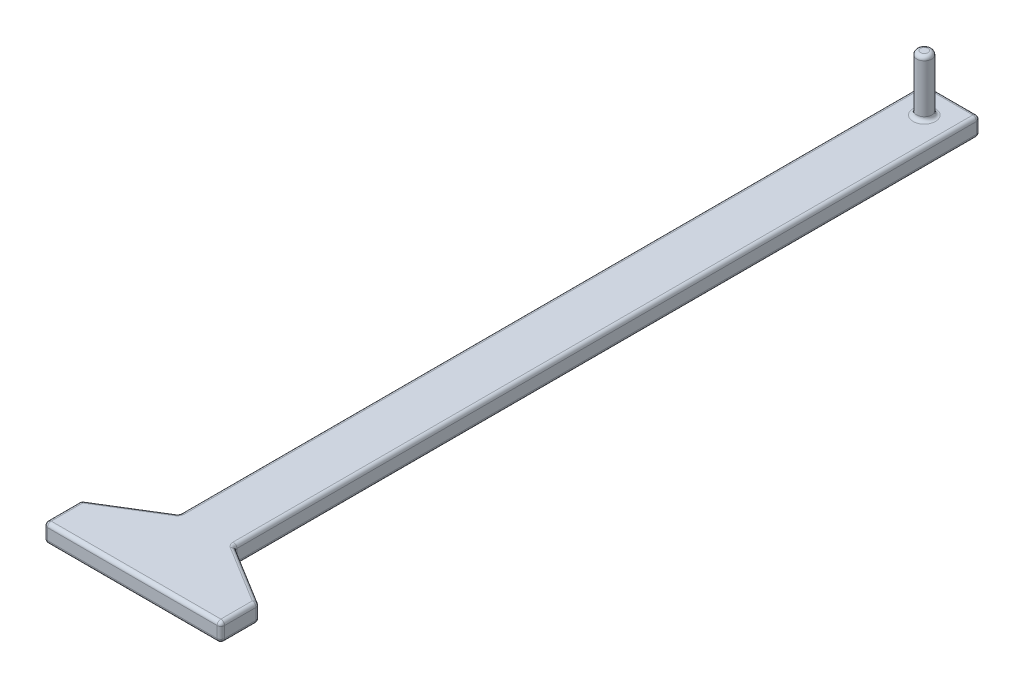
SolidWorks part; units mm, degrees
ref_plane "Front Plane" through (0, 0, 0) normal (0, 0, 1) x (1, 0, 0)
ref_plane "Top Plane" through (0, 0, 0) normal (0, 1, 0) x (1, 0, 0)
ref_plane "Right Plane" through (0, 0, 0) normal (1, 0, 0) x (0, 0, -1)
sketch "Sketch1" plane through (0, 0, 0) normal (0, 1, 0) x (1, 0, 0)
  line L0 (-15, 0) -> (-31.25, -10)
  line L1 (0, 0) -> (-15, 0)
  line L2 (0, 0) -> (0, 200)
  line L3 (0, 200) -> (-15, 200)
  line L4 (-15, 0) -> (-15, 200)
  line L5 (-31.25, -10) -> (16.25, -10)
  line L6 (16.25, -10) -> (0, 0)
  line L7 (16.25, -10) -> (16.25, -20)
  line L8 (16.25, -20) -> (-31.25, -20)
  line L9 (-31.25, -20) -> (-31.25, -10)
  dimension "D1" = 200
  dimension "D2" = 15
  dimension "D3" = 10
  dimension "D4" = 47.5
  dimension "D5" = 10
extrude "Boss-Extrude1" add sketch "Sketch1" along normal blind 5 contours L5 L6 L1 L0 | L4 L1 L2 L3 | L9 L8 L7 L5 region at (-7.5, 0, 5.8667) region at (-7.5, 0, -100) region at (-7.5, 0, 15)
sketch "Sketch4" plane through (0, 5, 0) normal (0, 1, 0) x (1, 0, 0)
  line L0 (-7.5, 200) -> (-7.5, 192.5) construction
  line L1 (0, 200) -> (-15, 200) construction
  line L2 (-7.5, 192.5) -> (-15, 192.5) construction
  line L3 (-15, 0) -> (-15, 200) construction
  circle A0 centre (-7.5, 192.5) radius 2
  dimension "D1" = 4
extrude "Boss-Extrude3" add sketch "Sketch4" along normal blind 15
fillet "Fillet5" radius 1 24 edges at (0, 2.5, 0) (0, 2.5, -200) (-15, 2.5, -200) (-15, 2.5, 0) (8.125, 0, 5) (0, 0, -100) (-7.5, 0, -200) (-15, 0, -100) (-23.125, 0, 5) (-7.5, 20, -190.5) (-23.125, 5, 5) (-15, 5, -100) (-7.5, 5, -200) (0, 5, -100) (8.125, 5, 5) (-7.5, 5, -190.5) (-31.25, 2.5, 10) (16.25, 2.5, 10) (-31.25, 0, 15) (-7.5, 0, 20) (16.25, 0, 15) (16.25, 5, 15) (-7.5, 5, 20) (-31.25, 5, 15)
fillet "Fillet6" radius 1 6 edges at (15.9571, 4.7071, 19.7071) (15.9571, 0.2929, 19.7071) (-30.9571, 4.7071, 19.7071) (-30.9571, 0.2929, 19.7071) (16.25, 2.5, 20) (-31.25, 2.5, 20)
